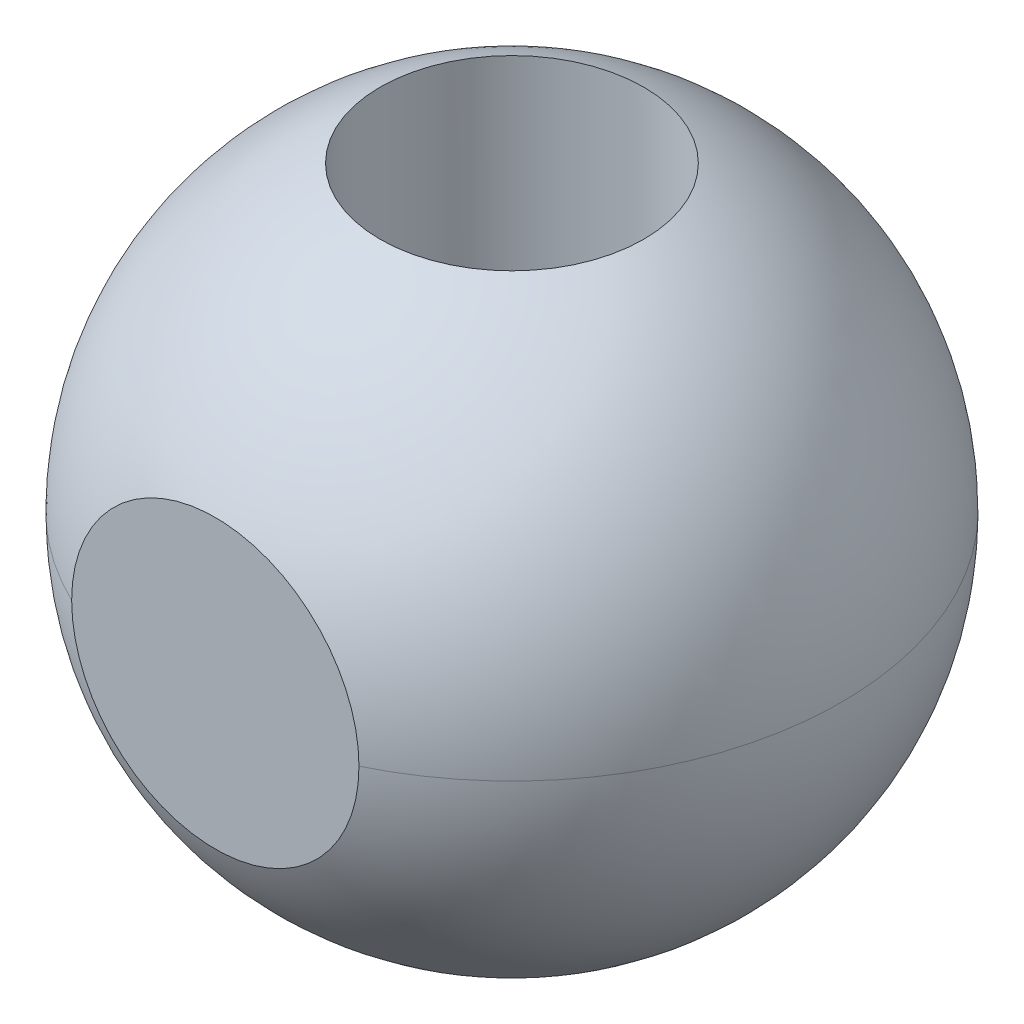
SolidWorks part; units mm, degrees
ref_plane "Front Plane" through (0, 0, 0) normal (0, 0, 1) x (1, 0, 0)
ref_plane "Top Plane" through (0, 0, 0) normal (0, 1, 0) x (1, 0, 0)
ref_plane "Right Plane" through (0, 0, 0) normal (1, 0, 0) x (0, 0, -1)
sketch "Sketch1" plane through (0, 0, 0) normal (0, 1, 0) x (1, 0, 0)
  circle A0 centre (0, 0) radius 12.7
  dimension "D1" = 25.4
extrude "Boss-Extrude1" add sketch "Sketch1" along normal blind 12.7 contours A0
fillet "Fillet1" radius 12.7 1 edges at (0, 12.7, 12.7)
sketch "Sketch2" plane through (0, 0, 0) normal (0, -1, 0) x (1, 0, 0)
  circle A0 centre (0, 0) radius 12.7
extrude "Boss-Extrude2" add sketch "Sketch2" along normal blind 12.7
fillet "Fillet2" radius 12.7 1 edges at (0, -12.7, -12.7)
sketch "Sketch3" plane through (0, 0, 0) normal (0, 1, 0) x (1, 0, 0)
  circle A0 centre (0, 0) radius 5.08
  dimension "D1" = 10.16
extrude "Cut-Extrude1" cut sketch "Sketch3" against normal through all both and the other way through all
sketch "Sketch5" plane through (0, 0, 0) normal (0, 1, 0) x (1, 0, 0)
  line L1 (-13.071, -11.43) -> (14.5088, -11.43)
  line L2 (-13.071, -11.43) -> (-13.071, -17.4427)
  line L3 (-13.071, -17.4427) -> (14.5088, -17.4427)
  line L4 (14.5088, -11.43) -> (14.5088, -17.4427)
  circle A0 centre (0, 0) radius 12.7 construction
  dimension "D1" = 11.43
extrude "Cut-Extrude2" cut sketch "Sketch5" against normal through all both and the other way through all
